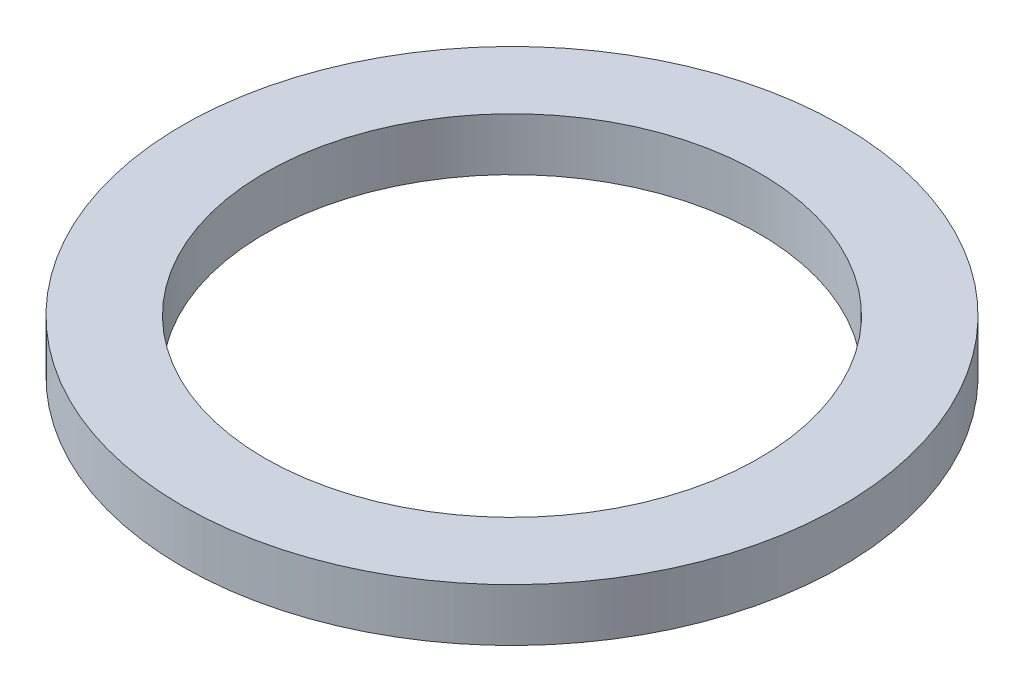
SolidWorks part; units mm, degrees
ref_plane "Front Plane" through (0, 0, 0) normal (0, 0, 1) x (1, 0, 0)
ref_plane "Top Plane" through (0, 0, 0) normal (0, 1, 0) x (1, 0, 0)
ref_plane "Right Plane" through (0, 0, 0) normal (1, 0, 0) x (0, 0, -1)
sketch "Sketch1" plane through (0, 0, 0) normal (0, 1, 0) x (1, 0, 0)
  circle A0 centre (0, 0) radius 50
  dimension "FLANGE_OD" = 100
extrude "Boss-Extrude1" add sketch "Sketch1" along normal blind 8
sketch "Sketch2" plane through (0, 0, 0) normal (0, 1, 0) x (1, 0, 0)
  circle A0 centre (0, 0) radius 37.5
  dimension "BORE_D" = 75
extrude "Cut-Extrude1" cut sketch "Sketch2" along normal through all
sketch "Sketch3" plane through (0, 8, 0) normal (0, 1, 0) x (1, 0, 0)
  circle A0 centre (0, 0) radius 20.7602 construction
  circle A1 centre (-20.7602, 0) radius 2.0878
  dimension "BOLT_D" = 4.1756
  dimension "BOLT_PCD" = 41.5204
extrude "Cut-Extrude2" cut sketch "Sketch3" against normal blind 5.0769 rebuild error yes
pattern_circular "CirPattern1" count 3 over 360 rebuild error yes
